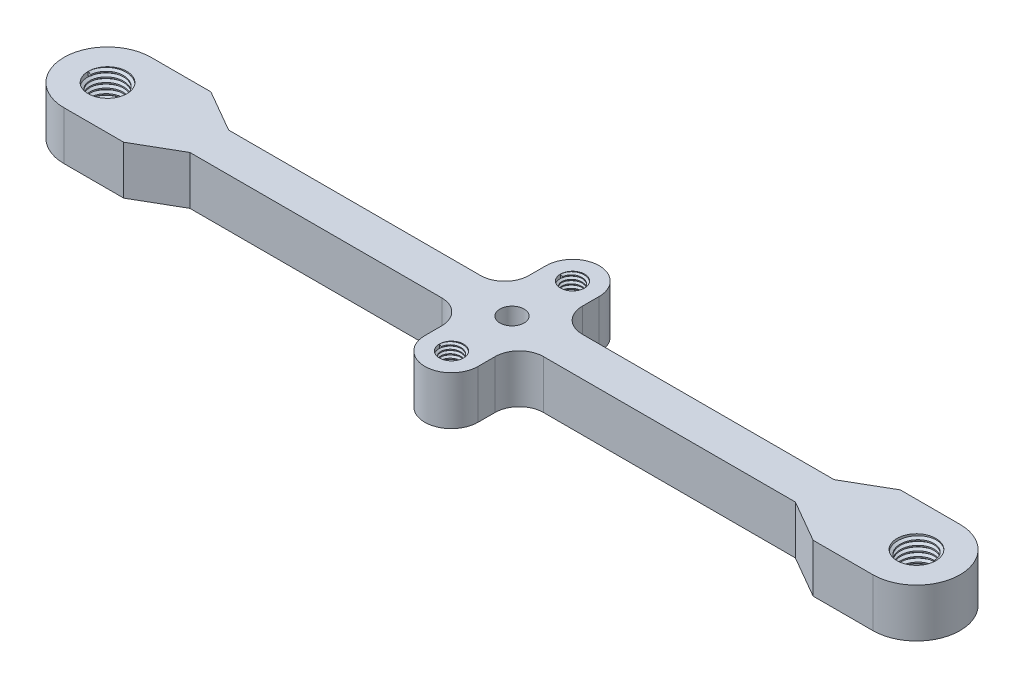
SolidWorks part; units mm, degrees
ref_plane "Front Plane" through (0, 0, 0) normal (0, 0, 1) x (1, 0, 0)
ref_plane "Top Plane" through (0, 0, 0) normal (0, 1, 0) x (1, 0, 0)
ref_plane "Right Plane" through (0, 0, 0) normal (1, 0, 0) x (0, 0, -1)
sketch "Sketch1" plane through (0, 0, 0) normal (0, 1, 0) x (1, 0, 0)
  line L0 (-83.5, 0) -> (83.5, 0) construction
  line L1 (-83.5, 9) -> (-71.1603, 9)
  line L2 (-83.5, -9) -> (-71.1603, -9)
  line L3 (-71.1603, 9) -> (-62.5, 4)
  line L4 (-62.5, 4) -> (-10.5, 4)
  line L5 (62.5, 4) -> (71.1603, 9)
  line L6 (71.1603, 9) -> (83.5, 9)
  line L7 (62.5, -4) -> (71.1603, -9)
  line L8 (-62.5, -4) -> (-10.5, -4)
  line L9 (-71.1603, -9) -> (-62.5, -4)
  line L10 (71.1603, -9) -> (83.5, -9)
  line L11 (0, -12.5) -> (0, 12.5) construction
  line L12 (5.5, -12.5) -> (5.5, -9)
  line L13 (-5.5, -12.5) -> (-5.5, -9)
  line L14 (10.5, -4) -> (62.5, -4)
  line L15 (-5.5, 12.5) -> (-5.5, 9)
  line L16 (5.5, 12.5) -> (5.4931, 9.0098)
  line L17 (10.4931, 4) -> (62.5, 4)
  circle A0 centre (0, 0) radius 2.5
  circle A1 centre (-83.5, 0) radius 4
  circle A2 centre (83.5, 0) radius 4
  circle A3 centre (0, -12.5) radius 2.5
  circle A4 centre (0, 12.5) radius 2.5
  arc A5 (-83.5, 9) -> (-83.5, -9) centre (-83.5, 0) ccw
  arc A6 (83.5, -9) -> (83.5, 9) centre (83.5, 0) ccw
  arc A7 (-5.5, -12.5) -> (5.5, -12.5) centre (0, -12.5) ccw
  circle A8 centre (83.5, 0) radius 9 construction
  circle A9 centre (-83.5, 0) radius 9 construction
  arc A10 (5.5, 12.4783) -> (-5.5, 12.5) centre (0, 12.5) ccw
  arc A11 (-5.5, -9) -> (-10.5, -4) centre (-10.5, -9) ccw
  circle A12 centre (0, -12.5) radius 5.5 construction
  circle A13 centre (0, 12.5) radius 5.5 construction
  arc A14 (-5.5, 9) -> (-10.5, 4) centre (-10.5, 9) cw
  arc A15 (5.4931, 9.0098) -> (10.4931, 4) centre (10.4931, 9) ccw
  arc A16 (5.5, -9) -> (10.5, -4) centre (10.5, -9) cw
  spline S0 degree 3 poles (1.6016, -6.3716) (1.6201, -6.3843) (1.6542, -6.4077) (1.6974, -6.4354) (1.8022, -6.5146) (1.9973, -6.0441) (2.3234, -5.731) (3.097, -4.4191) (4.0779, -2.542) (5.0049, 0.1119) (5.4355, 2.1021) (5.4973, 3.3996) (5.4892, 4.0015) (5.447, 4.57) (5.3277, 5.051) (5.1599, 5.4742) (4.9187, 5.8138) (4.6062, 6.0691) (4.1964, 6.185) (3.7283, 6.1371) (3.2365, 5.9653) (2.8294, 5.712) (2.5396, 5.5198) (2.5264, 5.2616) (2.746, 5.3023) (2.8502, 5.3669) (2.9218, 5.4113) knots 0 0 0 0 0.006701 0.012346 0.015713 0.043893 0.109433 0.185809 0.476111 0.761573 1.020998 1.084087 1.150838 1.201567 1.254676 1.298952 1.337276 1.378584 1.41743 1.461589 1.517763 1.571779 1.606709 1.618519 1.630914 1.658128 1.658128 1.658128 1.658128 weights 1 1 1 1 1 1 1 1 1 1 1 1 1 1 1 1 1 1 1 1 1 1 1 1 1 1 1 construction
  point P6 (0, 0)
  point P15 (-74.5, 0)
  point P20 (92.5, 0)
  point P26 (5.5, 12.5)
  point P35 (0, 0)
  point P36 (0, 0)
  point P40 (5.5, -12.5)
  point P51 (-5.5, -4)
  point P56 (5.4833, 4)
  point P59 (5.5, -4)
  dimension "D1" = 5
  dimension "D3" = 8
  dimension "D4" = 5
  dimension "D12" = 5
  dimension "D2" = 167
  dimension "D5" = 3
  dimension "D6" = 12.5
  dimension "D8" = 125
  dimension "D9" = 5
  dimension "D10" = 30
  dimension "D11" = 30
  dimension "D7" = 5
extrude "Boss-Extrude1" add sketch "Sketch1" along normal mid plane 10 contours L12 A16 L14 L7 L10 A6 L6 L5 L17 A15 L16 A10 L15 A14 L4 L3 L1 A5 L2 L9 L8 A11 L13 A7 A0 A1 A2 A3 A4 region at (-77.3301, 0, -7.1153)
thread "Thread1" pitch 1 method extrude profile "Thread Profile1" start angle 0, offset 0, length 0, pitch 1, diameter 8
ref_plane "Plane1" through (-87.5, 5, 0) normal (0, 0, 1) x (-1, 0, 0)
sketch "Thread Profile1" plane through (-87.5, 5, 0) normal (0, 0, 1) x (-1, 0, 0)
  line L0 (0, 0) -> (0, 1) construction
  line L11 (0, 0) -> (0, 0.875)
  line L12 (0, 0.875) -> (-0.5413, 0.5625)
  line L13 (-0.5413, 0.5625) -> (-0.5413, 0.3125)
  line L15 (-0.5413, 0.3125) -> (0, 0)
  line L17 (-0.5413, 0.4375) -> (0, 0.4375) construction
  point P2 (0, 0)
  dimension "Pitch" = 1
  dimension "Profile_Angle" = 60
  dimension "Profile_Land" = 0.25
  dimension "Profile_Height" = 0.5413
thread "Thread2" pitch 0.8 method extrude profile "Thread Profile2" start angle 0, offset 0, length 0, pitch 0.8, diameter 5
ref_plane "Plane2" through (-2.5, 5, 12.5) normal (0, 0, 1) x (-1, 0, 0)
sketch "Thread Profile2" plane through (-2.5, 5, 12.5) normal (0, 0, 1) x (-1, 0, 0)
  line L0 (0, 0) -> (0, 0.8) construction
  line L11 (0, 0) -> (0, 0.7)
  line L12 (0, 0.7) -> (-0.433, 0.45)
  line L13 (-0.433, 0.45) -> (-0.433, 0.25)
  line L15 (-0.433, 0.25) -> (0, 0)
  line L17 (-0.433, 0.35) -> (0, 0.35) construction
  point P2 (0, 0)
  dimension "Pitch" = 0.8
  dimension "Profile_Angle" = 60
  dimension "Profile_Land" = 0.2
  dimension "Profile_Height" = 0.433
thread "Thread3" pitch 0.8 method extrude profile "Thread Profile3" start angle 0, offset 0, length 0, pitch 0.8, diameter 5
ref_plane "Plane3" through (-2.5, 5, -12.5) normal (0, 0, 1) x (-1, 0, 0)
sketch "Thread Profile3" plane through (-2.5, 5, -12.5) normal (0, 0, 1) x (-1, 0, 0)
  line L0 (0, 0) -> (0, 0.8) construction
  line L11 (0, 0) -> (0, 0.7)
  line L12 (0, 0.7) -> (-0.433, 0.45)
  line L13 (-0.433, 0.45) -> (-0.433, 0.25)
  line L15 (-0.433, 0.25) -> (0, 0)
  line L17 (-0.433, 0.35) -> (0, 0.35) construction
  point P2 (0, 0)
  dimension "Pitch" = 0.8
  dimension "Profile_Angle" = 60
  dimension "Profile_Land" = 0.2
  dimension "Profile_Height" = 0.433
mirror "Mirror1" about plane through (0, 0, 0) normal (1, 0, 0) of "Thread1"
